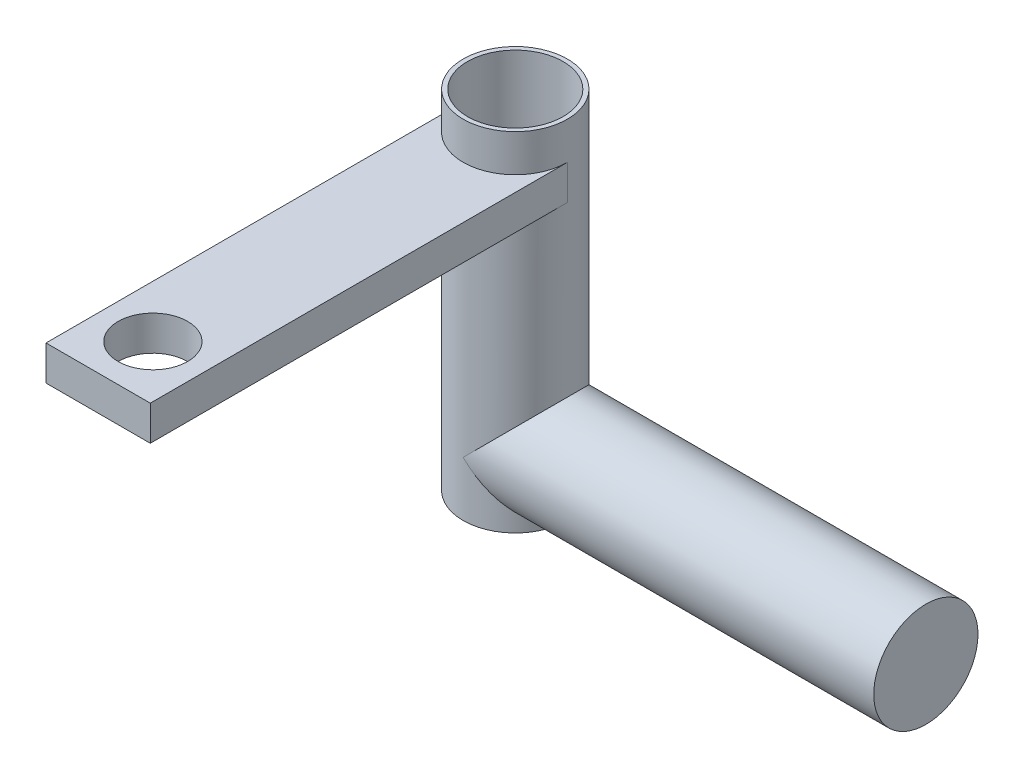
SolidWorks part; units mm, degrees
material "Alumina"
ref_plane "Front Plane" through (0, 0, 0) normal (0, 0, 1) x (1, 0, 0)
ref_plane "Top Plane" through (0, 0, 0) normal (0, 1, 0) x (1, 0, 0)
ref_plane "Right Plane" through (0, 0, 0) normal (1, 0, 0) x (0, 0, -1)
sketch "Sketch1" plane through (0, 0, 0) normal (0, 1, 0) x (1, 0, 0)
  circle A0 centre (0, 0) radius 9.525
  dimension "D1" = 19.05
extrude "Sleeve" add sketch "Sketch1" along normal blind 63.5
sketch "Sketch2" plane through (0, 0, 0) normal (0, 0, 1) x (1, 0, 0)
  line L0 (0, -40.1638) -> (0, 40.1638) construction
  line L1 (9.525, 56.675) -> (-9.525, 56.675)
  line L2 (9.525, 56.675) -> (9.525, 50.325)
  line L3 (9.525, 50.325) -> (-9.525, 50.325)
  line L4 (-9.525, 56.675) -> (-9.525, 50.325)
  line L5 (9.525, 56.675) -> (-9.525, 50.325) construction
  line L6 (9.525, 50.325) -> (-9.525, 56.675) construction
  point P0 (0, 53.5)
  dimension "D2" = 19.05
  dimension "D3" = 53.5
extrude "Bracket" add sketch "Sketch2" along normal blind 76.2
sketch "Sketch4" plane through (0, 0, 0) normal (0, 1, 0) x (1, 0, 0)
  line L0 (0, -40.1638) -> (0, 40.1638) construction
  circle A0 centre (0, -66.2) radius 6.35
  dimension "D1" = 12.7
  dimension "D2" = 66.2
extrude "Bracket Hole" cut sketch "Sketch4" along normal through all
sketch "Sketch5" plane through (0, 0, 0) normal (1, 0, 0) x (0, 0, -1)
  line L0 (0, 27.94) -> (0, -27.94) construction
  circle A0 centre (0, 10) radius 9.525
  dimension "D2" = 19.05
  dimension "D1" = 10
extrude "Shaft" add sketch "Sketch5" along normal blind 75
sketch "Sketch6" plane through (0, 0, 0) normal (0, 1, 0) x (1, 0, 0)
  circle A0 centre (0, 0) radius 8.7313
  dimension "D1" = 17.4625
extrude "Sleeve Hole" cut sketch "Sketch6" along normal through all
equation "\"shaftDiameter\"= 25.4 / 4 * 3mm"
equation "\"shaftLength\"= 75mm"
equation "\"sleeveDiameter\"= 25.4 / 4 * 3mm"
equation "\"sleeveLength\"= 2.5 * 25.4mm"
equation "\"bracketLength\" = 3 * 25.4mm"
equation "\"D1@Sketch1\"=\"sleeveDiameter\""
equation "\"D1@Sleeve\" = \"sleeveLength\""
equation "\"D3@Sketch2\"=\"sleeveLength\"-10"
equation "\"D1@Bracket\" = \"bracketLength\""
equation "\"tieBarHoleDiameter\"= 25.4 / 2mm"
equation "\"D1@Sketch4\"=\"tieBarHoleDiameter\""
equation "\"D2@Sketch4\"=\"bracketLength\"-10"
equation "\"D2@Sketch5\"=\"shaftDiameter\""
equation "\"D1@Shaft\" = \"shaftLength\""
equation "\"sleeveWallThickness\"= 25.4 / 16"
equation "\"D1@Sketch6\"=\"sleeveDiameter\"-\"sleeveWallThickness\""
